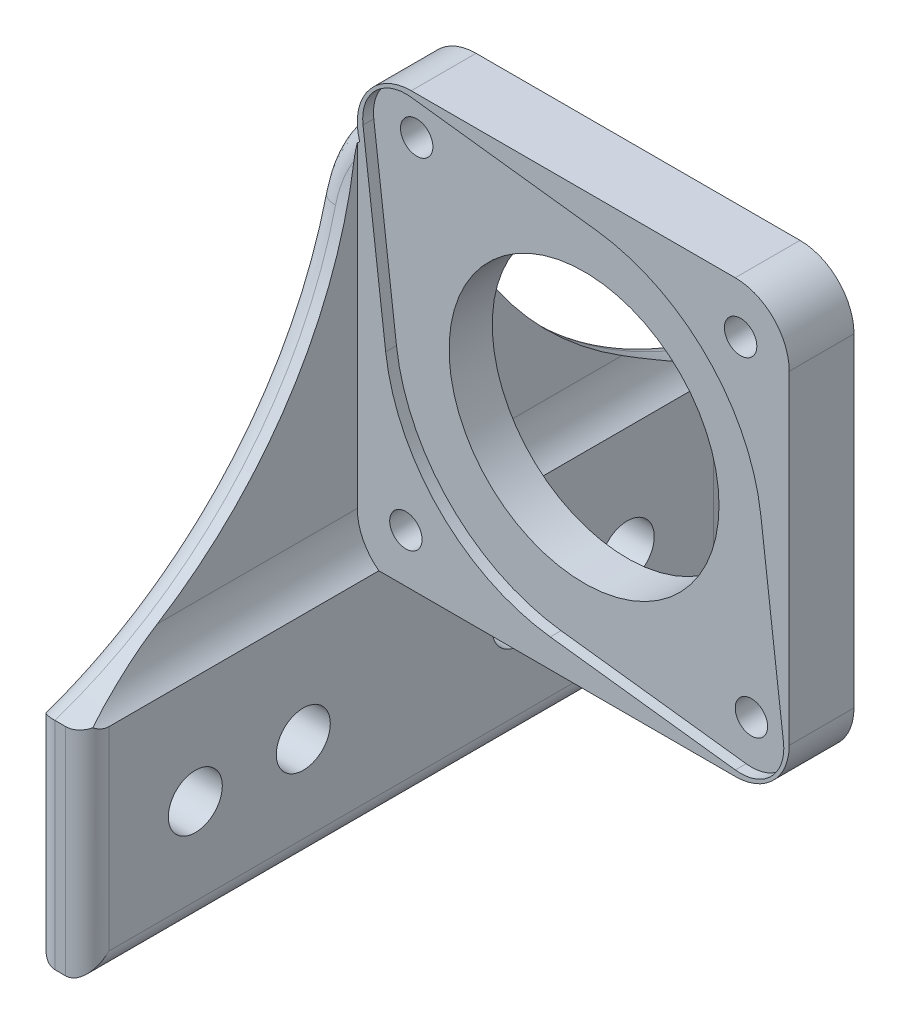
SolidWorks part; units mm, degrees
ref_plane "Front Plane" through (0, 0, 0) normal (0, 0, 1) x (1, 0, 0)
ref_plane "Top Plane" through (0, 0, 0) normal (0, 1, 0) x (1, 0, 0)
ref_plane "Right Plane" through (0, 0, 0) normal (1, 0, 0) x (0, 0, -1)
sketch "Sketch1" plane through (0, 0, 0) normal (0, 0, 1) x (1, 0, 0)
  line L0 (-15.5, 15.5) -> (15.5, 15.5) construction
  line L1 (-15, -20) -> (15, -20)
  line L2 (-20, -15) -> (-20, 15)
  line L3 (-15, 20) -> (15, 20)
  line L4 (20, -15) -> (20, 15)
  line L5 (-20, -20) -> (20, 20) construction
  line L6 (-20, 20) -> (20, -20) construction
  line L7 (-15.5, 15.5) -> (-15.5, -15.5) construction
  line L8 (-15.5, -15.5) -> (15.5, -15.5) construction
  line L9 (-20, -15) -> (-20, -20)
  line L10 (-20, -20) -> (-15, -20)
  circle A0 centre (0, 0) radius 12.5
  circle A1 centre (-15.5, 15.5) radius 1.5
  circle A2 centre (15.5, 15.5) radius 1.5
  circle A3 centre (-15.5, -15.5) radius 1.5
  circle A4 centre (15.5, -15.5) radius 1.5
  arc A5 (15, -20) -> (20, -15) centre (15, -15) ccw
  arc A6 (15, 20) -> (20, 15) centre (15, 15) cw
  arc A7 (-20, 15) -> (-15, 20) centre (-15, 15) cw
  point P0 (0, 0)
  dimension "D2" = 25
  dimension "D3" = 3
  dimension "D4" = 3
  dimension "D6" = 3
  dimension "D7" = 3
  dimension "D8" = 5
  dimension "D1" = 40
  dimension "D5" = 31
extrude "Boss-Extrude1" add sketch "Sketch1" along normal blind 3
ref_plane "Plane1" through (-20, 0, 0) normal (-1, 0, 0) x (0, 0, 1)
sketch "Sketch2" plane through (-20, 0, 0) normal (-1, 0, 0) x (0, 0, 1)
  line L1 (3, -40) -> (-27, -40)
  line L2 (-27, -40) -> (-27, -20)
  line L4 (-17, -20) -> (-17, -40) construction
  line L5 (-7, -20) -> (-7, -40) construction
  line L6 (-27, -30) -> (3, -30) construction
  line L17 (3, -40) -> (3, 15)
  line L18 (3, 15) -> (0, 15)
  arc A0 (0, 15) -> (-27, -20) centre (-39.533, 17.5826) cw
  circle A1 centre (-17, -30) radius 2.5
  circle A2 centre (-7, -30) radius 2.5
  dimension "D5" = 39.6172
  dimension "D7" = 5
  dimension "D8" = 5
  dimension "D1" = 55
  dimension "D2" = 30
  dimension "D3" = 10
  dimension "D4" = 10
  dimension "D6" = 20
extrude "Boss-Extrude2" add sketch "Sketch2" along normal blind 3 separate body
fillet "Fillet1" radius 10 1 edges at (-23, 15, 1.5)
ref_plane "Plane2" through (-20, -20, 0) normal (0, -1, 0) x (-1, 0, 0)
mirror "Mirror1" about plane through (15, -15, 3) normal (0, 0, 1) of "Boss-Extrude1", "Boss-Extrude2", "Fillet1"
sketch "Sketch3" plane through (0, 0, 6) normal (0, 0, 1) x (1, 0, 0)
  line L0 (19.4703, -15.0136) -> (17.3701, 2.1282)
  line L1 (15.0136, -19.4703) -> (-2.1282, -17.3701)
  line L2 (-15.0138, 19.4706) -> (2.1284, 17.3701)
  line L3 (-19.4706, 15.0138) -> (-17.3701, -2.1282)
  line L4 (-15.5003, 15.5003) -> (15.5, -15.5) construction
  line L5 (-12.5, 0) -> (12.5, 0) construction
  circle A0 centre (0, 0) radius 12.5
  arc A1 (-17.3701, -2.1282) -> (-2.1282, -17.3701) centre (0, 0) ccw
  arc A2 (-15.0138, 19.4706) -> (-19.4706, 15.0138) centre (-15.5003, 15.5003) ccw
  arc A3 (15.0136, -19.4703) -> (19.4703, -15.0136) centre (15.5, -15.5) ccw
  arc A4 (17.3701, 2.1282) -> (2.1284, 17.3701) centre (0, 0) ccw
  circle A7 centre (0, 0) radius 12.5 construction
  point P5 (0, 0)
  point P6 (0, 0)
  point P21 (0, 0)
  dimension "D1" = 25
  dimension "D2" = 17.5
  dimension "D3" = 8
  dimension "D4" = 8
  dimension "D5" = 43.841
  dimension "D6" = 45
  dimension "D7" = 17.1417
  dimension "D8" = 17.1417
  dimension "D9" = 17.142
extrude "Cut-Extrude1" cut sketch "Sketch3" against normal blind 1
sketch "Sketch5" plane through (0, 0, 0) normal (0, 0, 1) x (1, 0, 0)
  line L0 (19.4703, -15.0136) -> (17.3701, 2.1282)
  line L1 (15.0136, -19.4703) -> (-2.1282, -17.3701)
  line L2 (-15.0138, 19.4706) -> (2.1284, 17.3701)
  line L3 (-19.4706, 15.0138) -> (-17.3701, -2.1282)
  line L4 (-15.5003, 15.5003) -> (15.5, -15.5) construction
  line L5 (12.5, 0) -> (-12.5, 0) construction
  circle A0 centre (0, 0) radius 12.5
  arc A1 (-17.3701, -2.1282) -> (-2.1282, -17.3701) centre (0, 0) ccw
  arc A2 (-15.0138, 19.4706) -> (-19.4706, 15.0138) centre (-15.5003, 15.5003) ccw
  arc A3 (15.0136, -19.4703) -> (19.4703, -15.0136) centre (15.5, -15.5) ccw
  arc A4 (17.3701, 2.1282) -> (2.1284, 17.3701) centre (0, 0) ccw
  circle A7 centre (0, 0) radius 12.5 construction
  point P5 (0, 0)
  point P6 (0, 0)
  point P21 (0, 0)
  dimension "D1" = 25
  dimension "D2" = 17.5
  dimension "D3" = 8
  dimension "D4" = 8
  dimension "D5" = 43.841
  dimension "D6" = 45
  dimension "D7" = 17.1417
  dimension "D8" = 17.1417
  dimension "D9" = 17.142
extrude "Cut-Extrude3" cut sketch "Sketch5" along normal blind 1
sketch "Sketch6" plane through (-20, 0, 0) normal (1, 0, 0) x (0, 0, -1)
  line L0 (27, -20) -> (27, -40) construction
  line L1 (-33, -40) -> (27, -40)
  line L2 (-33, -40) -> (-33, -20)
  line L3 (-33, -20) -> (27, -20)
  line L4 (27, -40) -> (27, -20)
  line L5 (-55, -20) -> (55, -20) construction
  circle A0 centre (-23, -30) radius 2.5
  circle A1 centre (-13, -30) radius 2.5
  circle A2 centre (7, -30) radius 2.5
  circle A3 centre (17, -30) radius 2.5
  dimension "D1" = 5
extrude "Boss-Extrude3" add sketch "Sketch6" along normal blind 2
fillet "Fillet2" radius 5 2 edges at (-20, -20, -13.5) (-20, -20, 19.5)
fillet "Fillet3" radius 2 10 edges at (-22.4641, 11.0883, 6.4517) (-22.4641, 11.0883, -0.4517) (-23, -9.3771, 16.5036) (-23, -9.3771, -10.5036) (-23, -30, -27) (-18, -30, -27) (-23, -40, 3) (-18, -30, 33) (-23, -30, 33) (-18, -40, 3)
